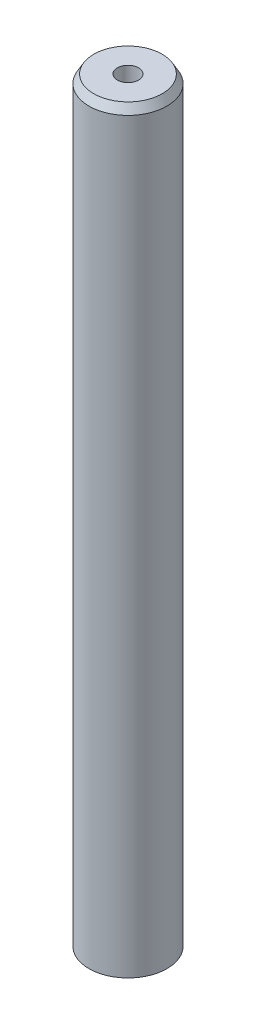
SolidWorks part; units mm, degrees
ref_plane "Front Plane" through (0, 0, 0) normal (0, 0, 1) x (1, 0, 0)
ref_plane "Top Plane" through (0, 0, 0) normal (0, 1, 0) x (1, 0, 0)
ref_plane "Right Plane" through (0, 0, 0) normal (1, 0, 0) x (0, 0, -1)
sketch "Sketch1" plane through (0, 0, 0) normal (0, 1, 0) x (1, 0, 0)
  circle A0 centre (0, 0) radius 12.5
  dimension "SHAFT_OD" = 25
extrude "Boss-Extrude1" add sketch "Sketch1" along normal blind 243.666
sketch "Sketch2" plane through (0, 0, 0) normal (0, 1, 0) x (1, 0, 0)
  circle A0 centre (0, 0) radius 3.4085
  dimension "BORE_D" = 6.8171
extrude "Cut-Extrude1" cut sketch "Sketch2" along normal through all
chamfer "Chamfer1" distance 2.6753 angle 29.646 2 edges at (0, 243.666, 12.5) (0, 0, 12.5) first distance on face at (0, 243.666, 12.5) first distance on face at (0, 0, 3.4085)
